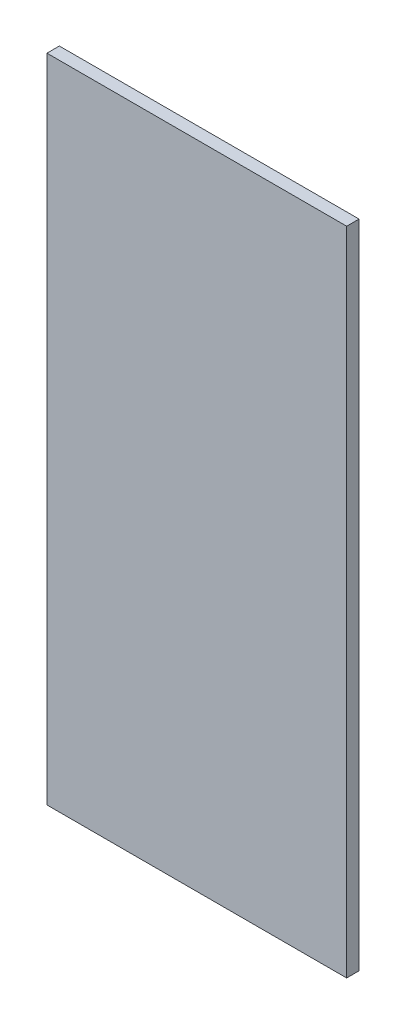
SolidWorks part; units mm, degrees
material "Perspex (TM) GS Acrylic Cast Sheet"
ref_plane "Front Plane" through (0, 0, 0) normal (0, 0, 1) x (1, 0, 0)
ref_plane "Top Plane" through (0, 0, 0) normal (0, 1, 0) x (1, 0, 0)
ref_plane "Right Plane" through (0, 0, 0) normal (1, 0, 0) x (0, 0, -1)
sketch "Sketch1" plane through (0, 0, 0) normal (0, 0, 1) x (1, 0, 0)
  line L1 (-72.5, -157.5) -> (72.5, -157.5)
  line L2 (-72.5, -157.5) -> (-72.5, 157.5)
  line L3 (-72.5, 157.5) -> (72.5, 157.5)
  line L4 (72.5, -157.5) -> (72.5, 157.5)
  line L5 (-72.5, -157.5) -> (72.5, 157.5) construction
  line L6 (-72.5, 157.5) -> (72.5, -157.5) construction
  point P0 (0, 0)
  dimension "D1" = 145
  dimension "D2" = 315
extrude "Boss-Extrude1" add sketch "Sketch1" along normal blind 6
equation "\"PCLength\"= 145mm'Length across I/O from PS to GPU"
equation "\"PCWidth\"= 340mm'Distance of longest part parallel to GPU(ussually GPU)"
equation "\"PCHeight\"= 180mm'Tallest point with mobo laying flat"
equation "\"WallThickness\"= 9mm'Thickness of each outer tank wall"
equation "\"ThermoBarrierThickness\"= 6mm'Thickness of barrier between hot side and cold side"
equation "\"HotSideGap\"= 36mm'Space in the hot side for a pump"
equation "\"PCClearance\"= 40mm'Clearance from top of tank to top of PC"
equation "\"RadiatorHeight\"= 275mm'Final Height from ground of radiators"
equation "\"D1@Sketch1\"=\"PCLength\""
equation "\"D2@Sketch1\"=\"RadiatorHeight\" + 40"
equation "\"D1@Boss-Extrude1\"=\"ThermoBarrierThickness\""
